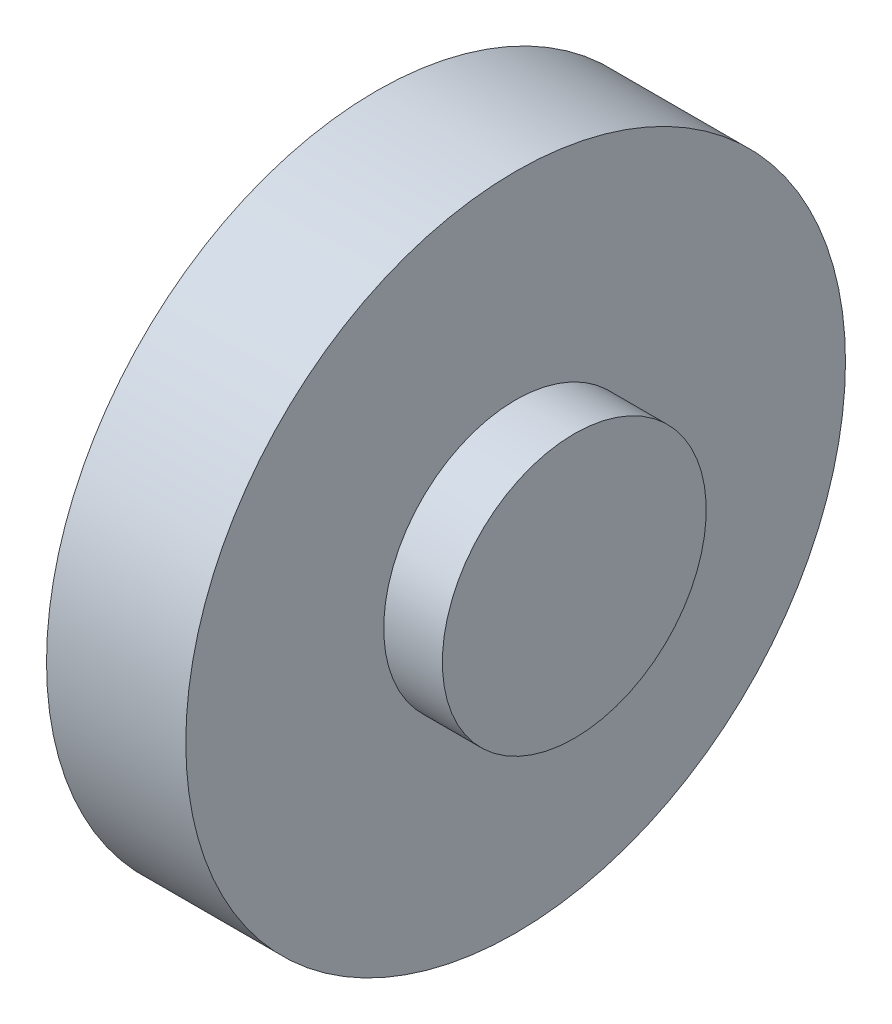
SolidWorks part; units mm, degrees
ref_plane "Front Plane" through (0, 0, 0) normal (0, 0, 1) x (1, 0, 0)
ref_plane "Top Plane" through (0, 0, 0) normal (0, 1, 0) x (1, 0, 0)
ref_plane "Right Plane" through (0, 0, 0) normal (1, 0, 0) x (0, 0, -1)
sketch "Sketch2" plane through (0, 0, 0) normal (0, 0, 1) x (1, 0, 0)
  line L0 (-78.8779, 0) -> (0, 0) construction
  line L1 (0, 0) -> (0, 10)
  line L2 (0, 10) -> (10, 10)
  line L3 (10, 10) -> (10, 45)
  line L4 (10, 45) -> (29, 45)
  line L5 (29, 45) -> (29, 18)
  line L9 (29, 18) -> (37, 18)
  line L10 (37, 18) -> (37, 0)
  line L11 (37, 0) -> (0, 0)
  line L12 (0, 0) -> (78.8779, 0) construction
  point P3 (0.8566, 0)
  dimension "D1" = 20
  dimension "D2" = 90
  dimension "D3" = 19
  dimension "D4" = 10
  dimension "D5" = 8
  dimension "D6" = 36
revolve "Revolve1" add sketch "Sketch2" angle 360 about L0
